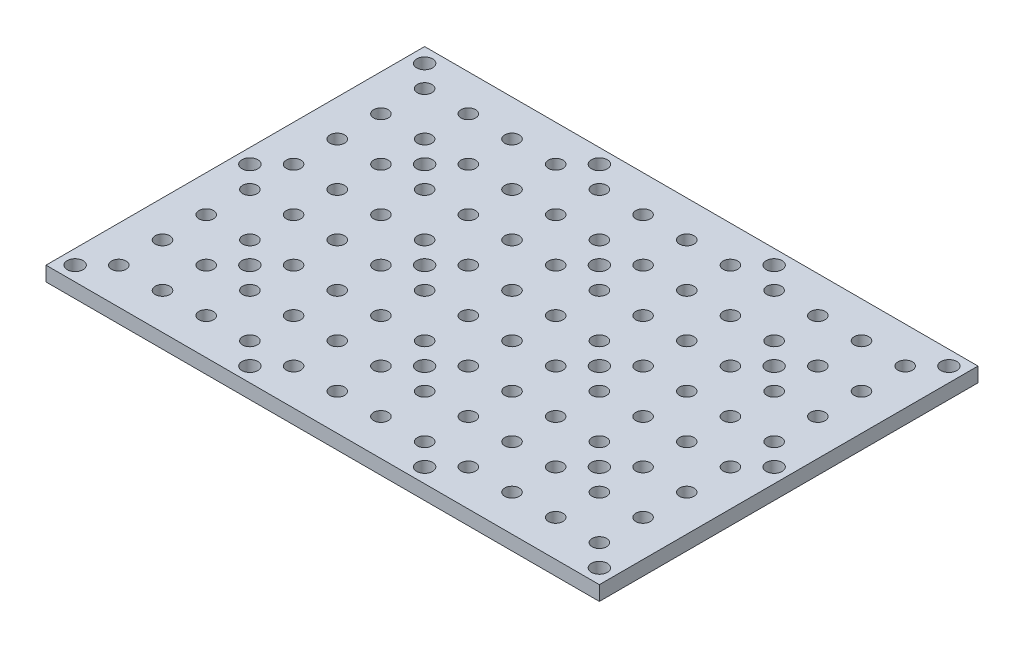
SolidWorks part; units mm, degrees
ref_plane "Front Plane" through (0, 0, 0) normal (0, 0, 1) x (1, 0, 0)
ref_plane "Top Plane" through (0, 0, 0) normal (0, 1, 0) x (1, 0, 0)
ref_plane "Right Plane" through (0, 0, 0) normal (1, 0, 0) x (0, 0, -1)
sketch "Sketch1" plane through (0, 0, 0) normal (0, 1, 0) x (1, 0, 0)
  line L1 (57, -39) -> (-57, -39)
  line L2 (57, -39) -> (57, 39)
  line L3 (57, 39) -> (-57, 39)
  line L4 (-57, -39) -> (-57, 39)
  line L5 (57, -39) -> (-57, 39) construction
  line L6 (57, 39) -> (-57, -39) construction
  point P0 (0, 0)
  dimension "D1" = 114
  dimension "D2" = 78
extrude "Boss-Extrude1" add sketch "Sketch1" along normal blind 3
sketch "Sketch2" plane through (0, 0, 0) normal (0, 1, 0) x (1, 0, 0)
  line L0 (0, -1.65) -> (0, 1.65) construction
  line L1 (-1.65, 0) -> (1.65, 0) construction
  circle A0 centre (-4.5, 4.5) radius 1.5
  dimension "D1" = 3
  dimension "D2" = 4.5
  dimension "D3" = 4.5
extrude "Cut-Extrude2" cut sketch "Sketch2" along normal through all
ref_axis "Axis1" through (-60.5, 0, 0) along (1, 0, 0)
ref_axis "Axis2" through (0, 0, 41.25) along (0, 0, -1)
pattern_linear "LPattern1" count 6 spacing 9 along (-1, 0, 0) count 4 spacing 9 along (0, 0, -1) of "Cut-Extrude2"
mirror "Mirror1" about plane through (0, 0, 0) normal (0, 0, 1) of "LPattern1", "Cut-Extrude2"
mirror "Mirror2" about plane through (0, 0, 0) normal (1, 0, 0) of "Cut-Extrude2", "Mirror1", "LPattern1"
hole_wizard "#4 Clearance Hole1" positions "Sketch3" profile "Sketch4" hole size "#4" standard "ANSI Inch" end condition through all
sketch "Sketch3" plane through (0, 3, 0) normal (0, 1, 0) x (1, 0, 0)
  line L1 (36, -18) -> (-36, -18) construction
  line L2 (36, -18) -> (36, 18) construction
  line L3 (36, 18) -> (-36, 18) construction
  line L4 (-36, -18) -> (-36, 18) construction
  line L5 (36, -18) -> (-36, 18) construction
  line L6 (36, 18) -> (-36, -18) construction
  line L7 (-1.65, 0) -> (1.65, 0) construction
  line L8 (0, -1.65) -> (0, 1.65) construction
  line L9 (-54, 36) -> (-18, 36) construction
  line L10 (-18, 36) -> (18, 36) construction
  line L11 (18, 36) -> (54, 36) construction
  line L12 (54, 36) -> (54, 0) construction
  line L13 (54, 0) -> (54, -36) construction
  line L14 (54, -36) -> (18, -36) construction
  line L15 (18, -36) -> (-18, -36) construction
  line L16 (-18, -36) -> (-54, -36) construction
  line L17 (-54, -36) -> (-54, 0) construction
  line L18 (-54, 0) -> (-54, 36) construction
  line L21 (-54, 0) -> (-18, 0) construction
  line L22 (-18, 0) -> (18, 0) construction
  line L23 (18, 0) -> (54, 0) construction
  line L26 (18, -36) -> (18, 0) construction
  line L27 (18, 0) -> (18, 36) construction
  line L30 (-18, -36) -> (-18, 0) construction
  line L31 (-18, 0) -> (-18, 36) construction
  point P1 (-36, 18)
  point P136 (36, -18)
  point P137 (36, 18)
  point P138 (-36, -18)
  point P149 (0, 18)
  point P151 (0, -18)
  point P152 (-54, 36)
  point P154 (-18, 36)
  point P156 (18, 36)
  point P158 (54, 36)
  point P160 (54, 0)
  point P162 (18, 0)
  point P164 (-18, 0)
  point P166 (-54, 0)
  point P168 (-54, -36)
  point P170 (-18, -36)
  point P172 (18, -36)
  point P174 (54, -36)
  point P229 (-54, 34.0981)
  point P230 (-18, 0.1366)
  dimension "D1" = 18
  dimension "D2" = 36
  dimension "D3" = 36
  dimension "D4" = 18
  dimension "D5" = 36
sketch "Sketch4" plane through (-36, 3, -18) normal (1, 0, 0) x (0, 0, 1)
  line L0 (0, 0) -> (0, 3)
  line L1 (0, 3) -> (1.6319, 3)
  line L2 (1.6319, 3) -> (1.6319, 0)
  line L5 (1.6319, 0) -> (0, 0)
  line L11 (0, -6.35) -> (0, 107.95) construction
  dimension "Thru Hole Dia." = 3.2639
  dimension "Thru Hole Depth" = 3
